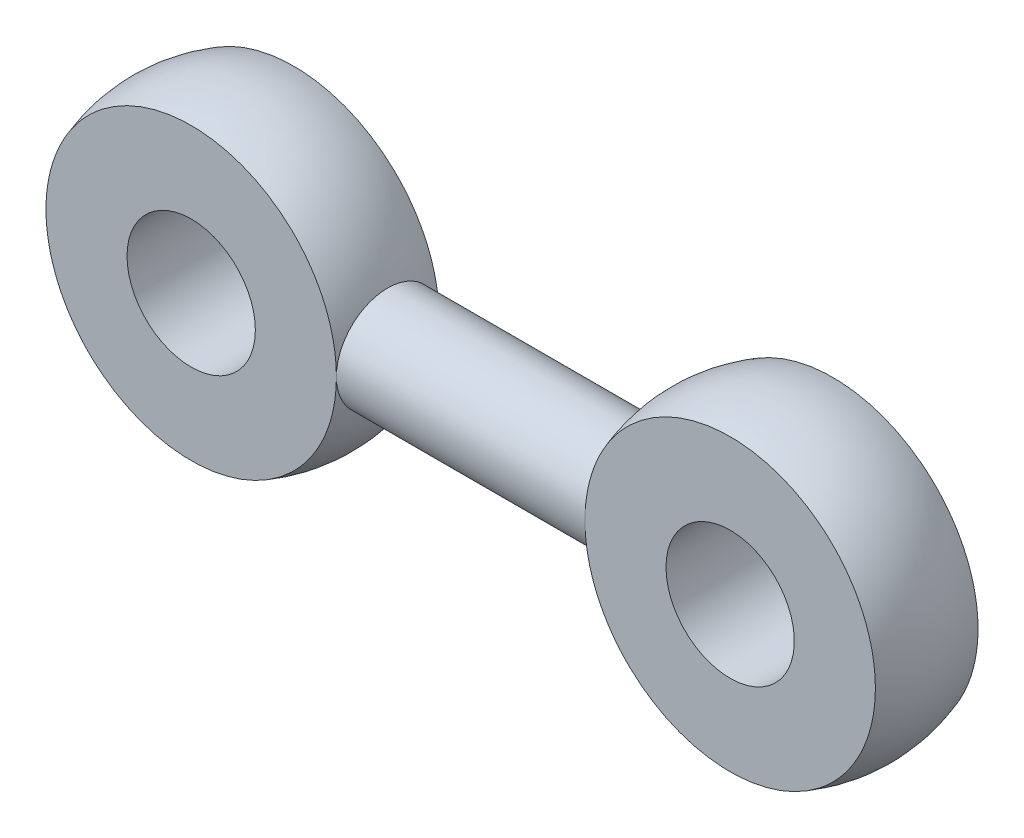
SolidWorks part; units mm, degrees
material "Alloy Steel"
ref_plane "Ön Düzlem" through (0, 0, 0) normal (0, 0, 1) x (1, 0, 0)
ref_plane "Üst Düzlem" through (0, 0, 0) normal (0, 1, 0) x (1, 0, 0)
ref_plane "Sağ Düzlem" through (0, 0, 0) normal (1, 0, 0) x (0, 0, -1)
sketch "Sketch1" plane through (0, 0, 0) normal (0, 0, 1) x (1, 0, 0)
  line L0 (6.2147, 0) -> (-5.6824, 0) construction
  line L1 (6, 0) -> (-27, 0)
  line L2 (-5.6569, 2) -> (-15.3431, 2)
  arc A0 (-27, 0) -> (-15.3431, 2) centre (-21, 0) cw
  arc A1 (-5.6569, 2) -> (6, 0) centre (0, 0) cw
  dimension "D2" = 6
  dimension "D3" = 6
  dimension "D1" = 21
  dimension "D4" = 2
revolve "Revolve1" add sketch "Sketch1" angle 360 about L0
sketch "Sketch4" plane through (0, 0, 0) normal (0, 1, 0) x (1, 0, 0)
  line L1 (-5.6569, 2) -> (5.6569, 2)
  line L3 (-5.6569, -2) -> (5.6569, -2)
  line L5 (-5.6569, 2) -> (-15.3431, 2) construction
  line L6 (-15.3431, -2) -> (-5.6569, -2) construction
  arc A0 (-5.6569, -2) -> (-5.6569, 2) centre (0, 0) ccw construction
  arc A1 (-5.6569, -2) -> (5.6569, -2) centre (0, 0) ccw
  arc A2 (5.6569, 2) -> (-5.6569, 2) centre (0, 0) ccw
extrude "Cut-Extrude4" cut sketch "Sketch4" against normal through all both and the other way through all
sketch "Sketch5" plane through (0, 0, -2) normal (0, 0, -1) x (-1, 0, 0)
  circle A0 centre (0, 0) radius 2.5
  dimension "D1" = 5
extrude "Cut-Extrude5" cut sketch "Sketch5" against normal up to next
sketch "Sketch8" plane through (0, 0, 0) normal (0, 1, 0) x (1, 0, 0)
  line L0 (-15.3431, 2) -> (-26.6569, 2)
  line L2 (-15.3431, -2) -> (-26.6569, -2)
  arc A0 (-15.3431, 2) -> (-26.6569, 2) centre (-21, 0) ccw
  arc A1 (-26.6569, -2) -> (-15.3431, -2) centre (-21, 0) ccw
extrude "Cut-Extrude10" cut sketch "Sketch8" against normal blind 10 and the other way blind 10
sketch "Sketch9" plane through (0, 0, -2) normal (0, 0, -1) x (-1, 0, 0)
  circle A0 centre (21, 0) radius 2.5
  dimension "D1" = 5
extrude "Cut-Extrude11" cut sketch "Sketch9" against normal blind 10
